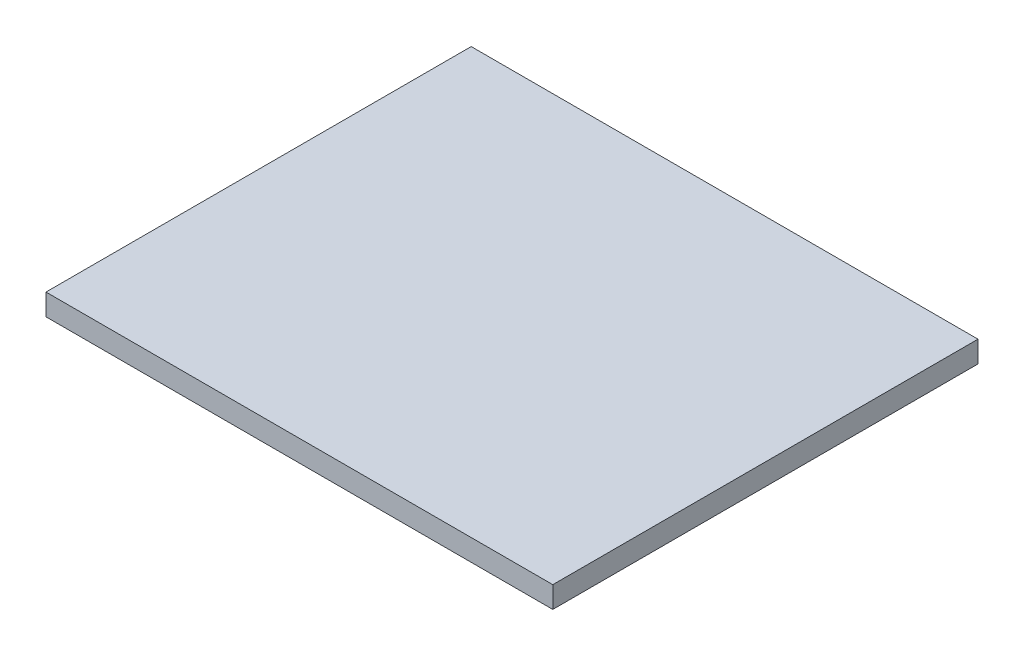
SolidWorks part; units mm, degrees
ref_plane "Front Plane" through (0, 0, 0) normal (0, 0, 1) x (1, 0, 0)
ref_plane "Top Plane" through (0, 0, 0) normal (0, 1, 0) x (1, 0, 0)
ref_plane "Right Plane" through (0, 0, 0) normal (1, 0, 0) x (0, 0, -1)
sketch "Sketch1" plane through (0, 0, 0) normal (0, 1, 0) x (1, 0, 0)
  line L6 (-29.5, 24.75) -> (29.5, 24.75)
  line L28 (-29.5, 24.75) -> (-29.5, -24.75)
  line L29 (-29.5, -24.75) -> (29.5, -24.75)
  line L30 (29.5, 24.75) -> (29.5, -24.75)
  line L31 (-29.5, 24.75) -> (29.5, -24.75) construction
  line L32 (-29.5, -24.75) -> (29.5, 24.75) construction
  circle A1 centre (0, 0) radius 3
  point P0 (0, 0)
  dimension "D3" = 6
  dimension "D1" = 59
  dimension "D2" = 49.5
extrude "Boss-Extrude1" add sketch "Sketch1" along normal blind 1.5
sketch "Sketch2" plane through (0, 0, -24.75) normal (0, 0, -1) x (-1, 0, 0)
  line L0 (-29.5, 1.5) -> (-29.5, 0) construction
  line L1 (-29.5, 1.5) -> (29.5, 1.5)
  line L2 (-29.5, 1.5) -> (-29.5, 2.5)
  line L4 (29.5, 1.5) -> (29.5, 2.5)
  line L5 (-1.18, 2.5) -> (0, 4)
  line L6 (0, 55) -> (0, -55) construction
  line L7 (1.18, 2.5) -> (0, 4)
  line L8 (1.18, 2.5) -> (2.36, 4)
  line L9 (3.54, 2.5) -> (2.36, 4)
  line L10 (3.54, 2.5) -> (4.72, 4)
  line L11 (5.9, 2.5) -> (4.72, 4)
  line L12 (5.9, 2.5) -> (7.08, 4)
  line L13 (8.26, 2.5) -> (7.08, 4)
  line L14 (8.26, 2.5) -> (9.44, 4)
  line L15 (10.62, 2.5) -> (9.44, 4)
  line L16 (10.62, 2.5) -> (11.8, 4)
  line L17 (12.98, 2.5) -> (11.8, 4)
  line L18 (12.98, 2.5) -> (14.16, 4)
  line L19 (15.34, 2.5) -> (14.16, 4)
  line L20 (15.34, 2.5) -> (16.52, 4)
  line L21 (17.7, 2.5) -> (16.52, 4)
  line L22 (17.7, 2.5) -> (18.88, 4)
  line L23 (20.06, 2.5) -> (18.88, 4)
  line L24 (20.06, 2.5) -> (21.24, 4)
  line L25 (22.42, 2.5) -> (21.24, 4)
  line L26 (22.42, 2.5) -> (23.6, 4)
  line L27 (24.78, 2.5) -> (23.6, 4)
  line L28 (24.78, 2.5) -> (25.96, 4)
  line L29 (27.14, 2.5) -> (25.96, 4)
  line L30 (27.14, 2.5) -> (28.32, 4)
  line L31 (29.5, 2.5) -> (28.32, 4)
  line L32 (-29.5, 2.5) -> (-28.32, 4)
  line L33 (-27.14, 2.5) -> (-28.32, 4)
  line L34 (-27.14, 2.5) -> (-25.96, 4)
  line L35 (-24.78, 2.5) -> (-25.96, 4)
  line L36 (-24.78, 2.5) -> (-23.6, 4)
  line L37 (-22.42, 2.5) -> (-23.6, 4)
  line L38 (-22.42, 2.5) -> (-21.24, 4)
  line L39 (-20.06, 2.5) -> (-21.24, 4)
  line L40 (-20.06, 2.5) -> (-18.88, 4)
  line L41 (-17.7, 2.5) -> (-18.88, 4)
  line L42 (-17.7, 2.5) -> (-16.52, 4)
  line L43 (-15.34, 2.5) -> (-16.52, 4)
  line L44 (-15.34, 2.5) -> (-14.16, 4)
  line L45 (-12.98, 2.5) -> (-14.16, 4)
  line L46 (-12.98, 2.5) -> (-11.8, 4)
  line L47 (-10.62, 2.5) -> (-11.8, 4)
  line L48 (-10.62, 2.5) -> (-9.44, 4)
  line L49 (-8.26, 2.5) -> (-9.44, 4)
  line L50 (-8.26, 2.5) -> (-7.08, 4)
  line L51 (-5.9, 2.5) -> (-7.08, 4)
  line L52 (-5.9, 2.5) -> (-4.72, 4)
  line L53 (-3.54, 2.5) -> (-4.72, 4)
  line L54 (-3.54, 2.5) -> (-2.36, 4)
  line L55 (-1.18, 2.5) -> (-2.36, 4)
  dimension "D1" = 1
  dimension "D2" = 1.5
  dimension "D3" = 13
extrude "Boss-Extrude2" add sketch "Sketch2" against normal up to surface (49.5 mm away) up to face at (0, 0.75, 24.75)
sketch "Sketch3" plane through (0, 0, 0) normal (0, -1, 0) x (-1, 0, 0)
  line L0 (0, 55) -> (0, -55) construction
  line L2 (-1.75, -2.4367) -> (-1.75, -5)
  line L3 (-1.75, -5) -> (1.75, -5)
  line L4 (1.75, -2.4367) -> (1.75, -5)
  arc A0 (1.75, -2.4367) -> (-1.75, -2.4367) centre (0, 0) ccw
  dimension "D2" = 6
  dimension "D1" = 3.5
  dimension "D3" = 5
  dimension "D4" = 1.75
extrude "Cut-Extrude1" cut sketch "Sketch3" against normal blind 1
sketch "Sketch4" plane through (29.5, 0, 0) normal (1, 0, 0) x (0, 0, -1)
  line L1 (-24.75, 4) -> (-24.75, 2.5) construction
  line L2 (-24.75, 4) -> (24.75, 4) construction
  line L3 (-24, 4) -> (-24.75, 4)
  line L4 (-24.75, 4) -> (-24.75, 3.25)
  arc A0 (-24.75, 3.25) -> (-24, 4) centre (-24, 3.25) cw
extrude "Cut-Extrude3" cut sketch "Sketch4" against normal through all
mirror "Mirror1" about plane through (0, 0, 0) normal (0, 0, 1) of "Cut-Extrude3"
sketch "Sketch5" plane through (0, 1.5, 0) normal (0, -1, 0) x (1, 0, 0)
  circle A0 centre (0, 0) radius 3
  dimension "D1" = 6
extrude "Boss-Extrude3" add sketch "Sketch5" along normal blind 0.5
sketch "Sketch6" plane through (0, 1, 0) normal (0, -1, 0) x (1, 0, 0)
  line L1 (1.75, 5) -> (-1.75, 5)
  line L2 (1.75, 5) -> (1.75, 2.4367)
  line L3 (1.75, 2.4367) -> (-1.75, 2.4367)
  line L4 (-1.75, 5) -> (-1.75, 2.4367)
extrude "Cut-Extrude4" cut sketch "Sketch6" against normal blind 0.5
chamfer "Chamfer3" distance 1.5 angle 45 1 edges at (0, 0, 5)
sketch "Sketch7" plane through (0, 0, 24.75) normal (0, 0, 1) x (1, 0, 0)
  line L1 (-29.5, 2.5) -> (29.5, 2.5)
  line L2 (-29.5, 2.5) -> (-29.5, 4.5865)
  line L3 (-29.5, 4.5865) -> (29.5, 4.5865)
  line L4 (29.5, 2.5) -> (29.5, 4.5865)
extrude "Cut-Extrude5" cut sketch "Sketch7" against normal through all
